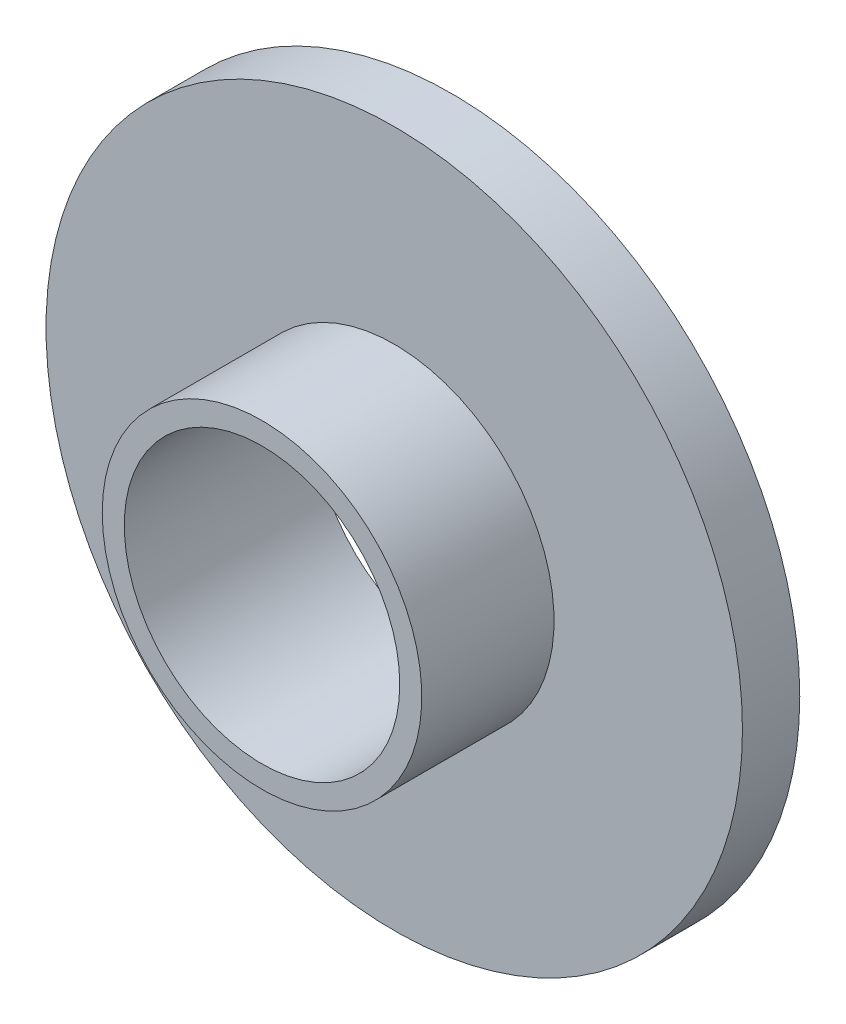
SolidWorks part; units mm, degrees
material "ABS"
ref_plane "正面" through (0, 0, 0) normal (0, 0, 1) x (1, 0, 0)
ref_plane "平面" through (0, 0, 0) normal (0, 1, 0) x (1, 0, 0)
ref_plane "右側面" through (0, 0, 0) normal (1, 0, 0) x (0, 0, -1)
sketch "ｽｹｯﾁ1" plane through (0, 0, 0) normal (0, 0, 1) x (1, 0, 0)
  circle A0 centre (0, 0) radius 7.9
  circle A1 centre (0, 0) radius 3.125
  circle A2 centre (0, 0) radius 3.625
  dimension "D1" = 15.8
  dimension "D2" = 6.25
  dimension "D3" = 7.25
extrude "ﾎﾞｽ - 押し出し1" add sketch "ｽｹｯﾁ1" along normal blind 1.3 contours A0 A2 | A2 A1 region at (-7.6766, 0, 0) region at (-3.5225, 0, 0)
extrude "ﾎﾞｽ - 押し出し2" add sketch "ｽｹｯﾁ1<3>" along normal blind 4.3 contours A2 A1 region at (-3.5225, 0, 0)
sketch "ｽｹｯﾁ1<3>" plane through (0, 0, 0) normal (0, 0, 1) x (1, 0, 0) same geometry as "ｽｹｯﾁ1"
